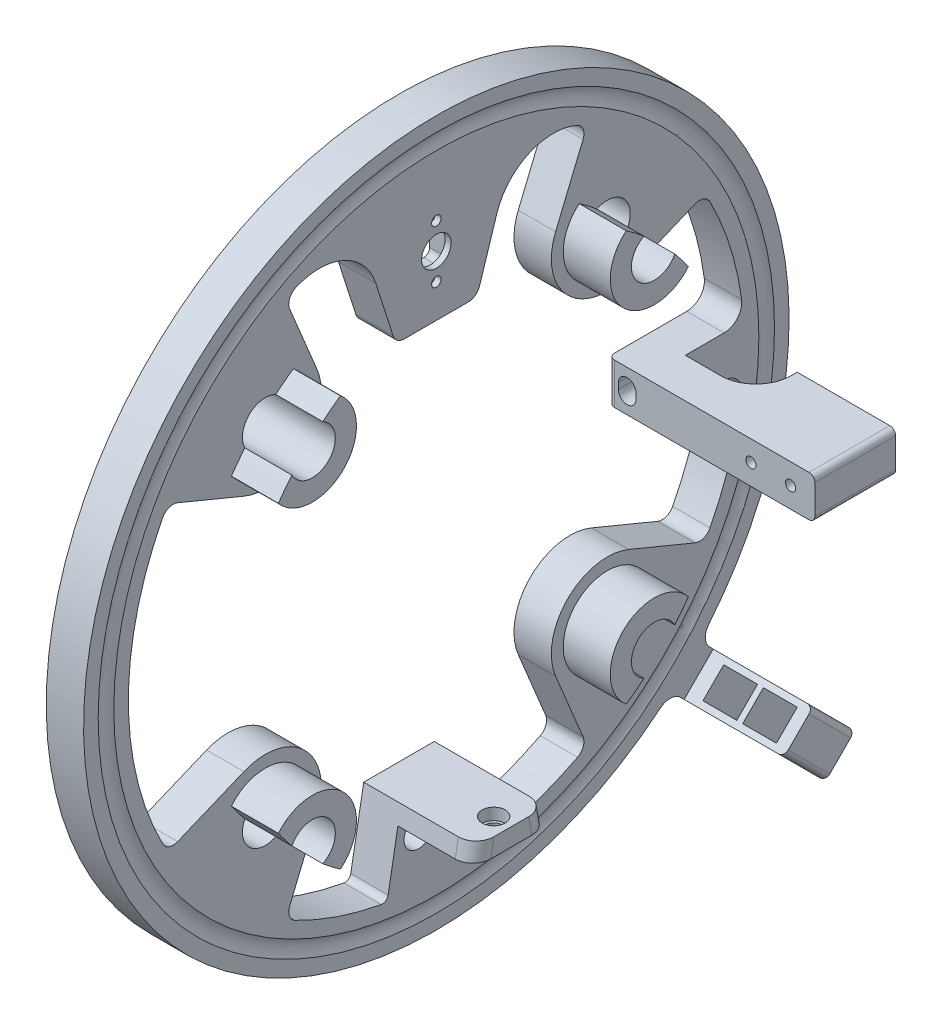
SolidWorks part; units mm, degrees
ref_plane "Front Plane" through (0, 0, 0) normal (0, 0, 1) x (1, 0, 0)
ref_plane "Top Plane" through (0, 0, 0) normal (0, 1, 0) x (1, 0, 0)
ref_plane "Right Plane" through (0, 0, 0) normal (1, 0, 0) x (0, 0, -1)
sketch "Sketch8" plane through (0, 0, 0) normal (1, 0, 0) x (0, 0, -1)
  line L1 (60, 60) -> (-60, 60) construction
  line L2 (60, 60) -> (60, -60) construction
  line L3 (60, -60) -> (-60, -60) construction
  line L4 (-60, 60) -> (-60, -60) construction
  line L5 (60, 60) -> (-60, -60) construction
  line L6 (60, -60) -> (-60, 60) construction
  point P0 (0, 0)
  dimension "D1" = 120
sketch "Sketch1" plane through (0, 0, 0) normal (1, 0, 0) x (0, 0, -1)
  line L0 (-60, 0) -> (-56.19, 0) construction
  line L1 (-56.19, 0) -> (-52.38, 0) construction
  circle A0 centre (0, 0) radius 56.19 construction
  circle A1 centre (0, 0) radius 60
  circle A2 centre (0, 0) radius 52.38
  dimension "D1" = 112.38
  dimension "D2" = 120
extrude "Boss-Extrude1" add sketch "Sketch1" along normal blind 6.35
sketch "Sketch2" plane through (0, 0, 0) normal (-1, 0, 0) x (0, 0, 1)
  line L0 (-20.2833, 32.7284) -> (-28.5792, 52.7563)
  line L1 (-60, -60) -> (60, -60) construction
  line L2 (-60, -60) -> (-60, 60) construction
  line L3 (-60, 60) -> (60, 60) construction
  line L4 (60, -60) -> (60, 60) construction
  line L5 (-60, -60) -> (60, 60) construction
  line L6 (-60, 60) -> (60, -60) construction
  line L7 (-28.5792, 52.7563) -> (-52.7563, 28.5792)
  line L8 (-52.7563, 28.5792) -> (-32.7284, 20.2833)
  circle A0 centre (0, 0) radius 52.38 construction
  arc A1 (-32.7284, 20.2833) -> (-20.2833, 32.7284) centre (-29.0833, 29.0833) ccw
  circle A3 centre (0, 0) radius 60 construction
  circle A5 centre (-29.0833, 29.0833) radius 11.25 construction
  circle A6 centre (0, 0) radius 52.78 construction
  point P0 (0, 0)
  point P10 (-40.6678, 40.6678)
  dimension "D2" = 19.05
  dimension "D3" = 45
  dimension "D5" = 105.56
  dimension "D4" = 22.5
  dimension "D1" = 120
extrude "Boss-Extrude2" add sketch "Sketch2" against normal up to surface (6.35 mm away) up to face at (6.35, 0, -60)
sketch "Sketch3" plane through (6.35, 0, 0) normal (1, 0, 0) x (0, 0, -1)
  circle A0 centre (29.0833, 29.0833) radius 7.5
  arc A2 (20.2833, 32.7284) -> (32.7284, 20.2833) centre (29.0833, 29.0833) ccw construction
  dimension "D1" = 15
extrude "Boss-Extrude3" add sketch "Sketch3" along normal blind 8
sketch "Sketch4" plane through (14.35, 0, 0) normal (1, 0, 0) x (0, 0, -1)
  circle A0 centre (29.0833, 29.0833) radius 3.9
  circle A1 centre (29.0833, 29.0833) radius 7.5 construction
  dimension "D1" = 7.8
extrude "Cut-Extrude2" cut sketch "Sketch4" against normal through all contours A0
fillet "Fillet5" radius 2 2 edges at (3.175, 45.6727, -25.6451) (3.175, 25.6451, -45.6727)
ref_axis "Axis1" through (6.35, 0, 0) along (-1, 0, 0)
pattern_circular "CirPattern1" count 4 every 90 about axis through (6.35, 0, 0) along (-1, 0, 0) of "Boss-Extrude3", "Boss-Extrude2", "Cut-Extrude2", "Fillet5"
sketch "Sketch5" plane through (0, 0, 0) normal (-1, 0, 0) x (0, 0, 1)
  line L0 (5.6388, 40) -> (-10.2587, 40) construction
  line L1 (0, 0) -> (0, 60) construction
  line L2 (15.871, 57.8629) -> (-15.871, 57.8629)
  line L3 (15.871, 57.8629) -> (6.9028, 29.8063)
  line L4 (6.9028, 29.8063) -> (-6.9028, 29.8063)
  line L5 (-15.871, 57.8629) -> (-6.9028, 29.8063)
  circle A0 centre (0, 40) radius 2.5
  circle A1 centre (0, 35.5) radius 0.8
  circle A2 centre (0, 44.5) radius 0.8
  circle A3 centre (0, 0) radius 60 construction
  dimension "D2" = 9
  dimension "D3" = 5
  dimension "D4" = 1.6
  dimension "D1" = 40
extrude "Boss-Extrude5" add sketch "Sketch5" against normal up to surface (6.35 mm away) up to face at (6.35, 36.5833, 29.0833)
sketch "Sketch6" plane through (0, 0, 0) normal (-1, 0, 0) x (0, 0, 1)
  line L1 (5.2, 33.8) -> (-5.2, 33.8)
  line L2 (5.2, 33.8) -> (5.2, 46.2)
  line L3 (5.2, 46.2) -> (-5.2, 46.2)
  line L4 (-5.2, 33.8) -> (-5.2, 46.2)
  line L5 (5.2, 33.8) -> (-5.2, 46.2) construction
  line L6 (5.2, 46.2) -> (-5.2, 33.8) construction
  point P0 (0, 40)
  dimension "D1" = 12.4
  dimension "D2" = 10.4
extrude "Cut-Extrude1" cut sketch "Sketch6" against normal offset from surface (5.35 mm away) 1 up to face at (6.35, 5.5549, 0)
fillet "Fillet1" radius 1 4 edges at (2.675, 33.8, 5.2) (2.675, 46.2, -5.2) (2.675, 46.2, 5.2) (2.675, 33.8, -5.2)
fillet "Fillet2" radius 10.08 2 edges at (3.175, 50.5974, -13.5486) (3.175, 50.5974, 13.5486)
fillet "Fillet3" radius 2 2 edges at (3.175, 29.8063, -6.9028) (3.175, 29.8063, 6.9028)
sketch "Sketch14" plane through (0, 0, 0) normal (-1, 0, 0) x (0, 0, 1)
  line L0 (-59.8978, 0) -> (0, 0) construction
  line L1 (-35.63, 3.5) -> (-59.8978, 3.5)
  line L2 (-35.63, 3.5) -> (-35.63, -3.5)
  line L3 (-35.63, -3.5) -> (-59.8978, -3.5)
  line L4 (-59.8978, 3.5) -> (-59.8978, -3.5)
  line L5 (-35.63, 3.5) -> (-59.8978, -3.5) construction
  line L6 (-35.63, -3.5) -> (-59.8978, 3.5) construction
  circle A0 centre (0, 0) radius 60 construction
  arc A2 (-46.5462, 24.0232) -> (-46.5462, -24.0232) centre (0, 0) ccw construction
  point P0 (-47.7639, 0)
  point P7 (-52.38, 0)
  dimension "D2" = 16.75
  dimension "D1" = 7
extrude "Boss-Extrude8" add sketch "Sketch14" against normal up to surface (6.35 mm away) up to face at (6.35, 6.7511, 0)
fillet "Fillet7" radius 3 2 edges at (3.175, -3.5, -52.2629) (3.175, 3.5, -52.2629)
sketch "Sketch7" plane through (0, 0, 0) normal (0, 1, 0) x (1, 0, 0)
  line L0 (8.636, 56.19) -> (-2.286, 56.19) construction
  line L1 (3.175, 60) -> (3.175, -60) construction
  line L2 (6.35, 60) -> (0, 60) construction
  line L3 (0, -60) -> (6.35, -60) construction
  circle A0 centre (8.636, 56.19) radius 2.645
  circle A1 centre (-2.286, 56.19) radius 2.645
  dimension "D1" = 5.29
  dimension "D2" = 56.19
  dimension "D3" = 10.922
revolve "Cut-Revolve1" cut sketch "Sketch7" angle 360 about axis through (6.35, 0, 0) along (-1, 0, 0)
sketch "Sketch9" plane through (0, 0, 0) normal (-1, 0, 0) x (0, 0, 1)
  line L0 (-54.1628, -49.2131) -> (-49.2131, -54.1628)
  line L1 (-49.2131, -54.1628) -> (-39.8793, -44.829)
  line L2 (-39.8793, -44.829) -> (-44.829, -39.8793)
  line L3 (-44.829, -39.8793) -> (-54.1628, -49.2131)
  line L4 (-60, -60) -> (60, 60) construction
  circle A0 centre (0, 0) radius 60 construction
  point P8 (-51.688, -51.688)
  dimension "D1" = 13.2
  dimension "D2" = 7
extrude "Boss-Extrude6" add sketch "Sketch9" against normal up to surface (6.35 mm away) up to face at (6.35, 0, -60)
fillet "Fillet6" radius 2.54 2 edges at (3.175, -44.829, -39.8793) (3.175, -39.8793, -44.829)
sketch "Sketch10" plane through (6.35, 0, 0) normal (1, 0, 0) x (0, 0, -1)
  line L0 (49.2131, -54.1628) -> (54.1628, -49.2131)
  line L1 (49.2131, -54.1628) -> (42.142, -47.0918)
  line L2 (54.1628, -49.2131) -> (47.0918, -42.142)
  line L3 (42.142, -47.0918) -> (47.0918, -42.142)
  dimension "D1" = 10
extrude "Boss-Extrude7" add sketch "Sketch10" along normal blind 17
sketch "Sketch11" plane through (0, -44.6169, -44.6169) normal (0, 0.7071, 0.7071) x (1, 0, 0)
  line L0 (6.35, 3.5) -> (6.35, -3.5) construction
  line L1 (8.85, 2.5) -> (14.6, 2.5)
  line L2 (8.85, 2.5) -> (8.85, -2.5)
  line L3 (8.85, -2.5) -> (14.6, -2.5)
  line L4 (14.6, 2.5) -> (14.6, -2.5)
  line L5 (8.85, 2.5) -> (14.6, -2.5) construction
  line L6 (8.85, -2.5) -> (14.6, 2.5) construction
  line L7 (23.35, 0) -> (6.35, 0) construction
  line L8 (23.35, 3.5) -> (23.35, -3.5) construction
  line L10 (15.6, 2.5) -> (21.35, 2.5)
  line L11 (15.6, 2.5) -> (15.6, -2.5)
  line L12 (15.6, -2.5) -> (21.35, -2.5)
  line L13 (21.35, 2.5) -> (21.35, -2.5)
  line L14 (15.6, 2.5) -> (21.35, -2.5) construction
  line L15 (15.6, -2.5) -> (21.35, 2.5) construction
  point P0 (11.725, 0)
  point P11 (18.475, 0)
  dimension "D1" = 2.5
  dimension "D2" = 5.75
  dimension "D3" = 5
  dimension "D4" = 1
extrude "Cut-Extrude3" cut sketch "Sketch11" against normal offset from surface (8.5 mm away) 1.5 up to face at (11.675, -51.688, -51.688)
sketch "Sketch12" plane through (0, -50.6273, -50.6273) normal (0, 0.7071, 0.7071) x (1, 0, 0)
  line L0 (15.6, -2.5) -> (21.35, 2.5) construction
  line L1 (8.85, -2.5) -> (14.6, 2.5) construction
  circle A0 centre (11.725, 0) radius 0.875
  circle A1 centre (18.475, 0) radius 0.875
  dimension "D1" = 1.75
extrude "Cut-Extrude4" cut sketch "Sketch12" against normal through all
sketch "Sketch15" plane through (6.35, 0, 0) normal (1, 0, 0) x (0, 0, -1)
  line L0 (48.9503, -3.5) -> (35.63, -3.5) construction
  line L1 (35.63, 3.5) -> (49.38, 3.5)
  line L2 (35.63, 3.5) -> (35.63, -3.5)
  line L3 (35.63, -3.5) -> (49.38, -3.5)
  line L4 (49.38, 3.5) -> (49.38, -3.5)
  dimension "D1" = 13.75
extrude "Boss-Extrude9" add sketch "Sketch15" along normal blind 28.75
sketch "Sketch16" plane through (0, 0, -49.38) normal (0, 0, -1) x (-1, 0, 0)
  line L0 (-35.1, 0) -> (-10.5477, 0) construction
  line L1 (-28.1, -2.5) -> (-33.85, -2.5)
  line L2 (-28.1, -2.5) -> (-28.1, 2.5)
  line L3 (-28.1, 2.5) -> (-33.85, 2.5)
  line L4 (-33.85, -2.5) -> (-33.85, 2.5)
  line L5 (-28.1, -2.5) -> (-33.85, 2.5) construction
  line L6 (-28.1, 2.5) -> (-33.85, -2.5) construction
  line L7 (-21.35, -2.5) -> (-27.1, -2.5)
  line L8 (-21.35, -2.5) -> (-21.35, 2.5)
  line L9 (-21.35, 2.5) -> (-27.1, 2.5)
  line L10 (-27.1, -2.5) -> (-27.1, 2.5)
  line L11 (-21.35, -2.5) -> (-27.1, 2.5) construction
  line L12 (-21.35, 2.5) -> (-27.1, -2.5) construction
  line L13 (-35.1, 3.5) -> (-35.1, -3.5) construction
  line L14 (-6.35, 0) -> (0, 0) construction
  line L15 (-14.6, -42.8491) -> (-8.85, -42.8491) construction
  line L18 (-6.35, -3.5) -> (-6.35, 3.5) construction
  point P0 (-30.975, 0)
  point P5 (-24.225, 0)
  dimension "D1" = 5
  dimension "D3" = 1
  dimension "D4" = 15
extrude "Cut-Extrude5" cut sketch "Sketch16" against normal offset from surface (12.25 mm away) 1.5 up to face at (17.55, 0, -35.63)
sketch "Sketch17" plane through (0, 0, -37.13) normal (0, 0, -1) x (-1, 0, 0)
  line L0 (-28.1, -2.5) -> (-33.85, 2.5) construction
  line L1 (-27.1, 2.5) -> (-21.35, -2.5) construction
  circle A0 centre (-30.975, 0) radius 0.875
  circle A1 centre (-24.225, 0) radius 0.875
  dimension "D1" = 1.75
extrude "Cut-Extrude6" cut sketch "Sketch17" against normal through all
fillet "Fillet8" radius 1 6 edges at (0, 0, -35.63) (0, -51.688, -51.688) (23.35, -45.6776, -50.6273) (23.35, -50.6273, -45.6776) (35.1, 3.5, -42.505) (35.1, -3.5, -42.505)
sketch "Sketch18" plane through (0, 0, 0) normal (0, 0, 1) x (1, 0, 0)
  line L1 (3.175, -0.5) -> (3.175, 0.5) construction
  line L3 (1.675, -0.5) -> (1.675, 0.5)
  line L4 (4.675, -0.5) -> (4.675, 0.5)
  line L5 (0, 0) -> (6.35, 0) construction
  line L6 (0, 60) -> (0, -60) construction
  line L7 (6.35, -60) -> (6.35, 60) construction
  arc A0 (1.675, -0.5) -> (4.675, -0.5) centre (3.175, -0.5) ccw
  arc A1 (4.675, 0.5) -> (1.675, 0.5) centre (3.175, 0.5) ccw
  point P2 (3.175, 0)
  dimension "D1" = 1.5
  dimension "D2" = 1
extrude "Cut-Extrude7" cut sketch "Sketch18" against normal through all
sketch "Sketch19" plane through (0, 0, 0) normal (-1, 0, 0) x (0, 0, 1)
  line L0 (0, -60) -> (0, -32.7201) construction
  line L1 (6, -38.38) -> (-6, -38.38)
  line L2 (6, -38.38) -> (8.5, -52.38)
  line L3 (8.5, -52.38) -> (-8.5, -52.38)
  line L4 (-6, -38.38) -> (-8.5, -52.38)
  line L5 (-60, -60) -> (60, -60) construction
  arc A0 (-24.0232, -46.5462) -> (24.0232, -46.5462) centre (0, 0) ccw construction
  circle A1 centre (3, -44) radius 2.5
  circle A2 centre (-3, -44) radius 2.5
  dimension "D1" = 5
  dimension "D2" = 16
  dimension "D5" = 6
  dimension "D3" = 12
  dimension "D4" = 17
  dimension "D6" = 5.62
extrude "Boss-Extrude10" add sketch "Sketch19" against normal up to surface (6.35 mm away) up to face at (6.35, 29.0833, -36.5833)
fillet "Fillet9" radius 1 2 edges at (3.175, -51.7054, -8.3795) (3.175, -51.7054, 8.3795)
sketch "Sketch20" plane through (14.35, 0, 0) normal (1, 0, 0) x (0, 0, -1)
  circle A0 centre (0, 0) radius 42.5
  circle A1 centre (0, 0) radius 60
  arc A2 (46.3255, -38.1306) -> (38.1306, -46.3255) centre (0, 0) ccw construction
  dimension "D1" = 85
extrude "Cut-Extrude8" cut sketch "Sketch20" against normal up to surface (8 mm away) and the other way blind 4 up to face at (6.35, -1.7736, -7.0879)
fillet "Fillet10" radius 6 1 edges at (18.35, 0, -42.5)
sketch "Sketch23" plane through (6.35, 0, 0) normal (1, 0, 0) x (0, 0, -1)
  line L0 (6, -38.38) -> (-6, -38.38)
  line L1 (-6, -38.38) -> (-6.5357, -41.38)
  line L2 (-8.2049, -50.7274) -> (-6, -38.38) construction
  line L3 (-6.5357, -41.38) -> (6.5357, -41.38)
  line L4 (6, -38.38) -> (8.2049, -50.7274) construction
  line L5 (6.5357, -41.38) -> (6, -38.38)
  dimension "D1" = 3
extrude "Boss-Extrude11" add sketch "Sketch23" along normal blind 12.75
fillet "Fillet11" radius 3 2 edges at (19.1, -39.88, -6.2679) (19.1, -39.88, 6.2679)
sketch "Sketch24" plane through (0, -38.38, 0) normal (0, 1, 0) x (1, 0, 0)
  line L0 (16.1, 0) -> (0, 0) construction
  line L1 (0, -6) -> (0, 6) construction
  circle A0 centre (16.1, 0) radius 1.95
  dimension "D1" = 3.9
  dimension "D2" = 9.75
extrude "Cut-Extrude9" cut sketch "Sketch24" against normal offset from surface (2 mm away) 1 up to face at (14.0571, -41.38, 0)
sketch "Sketch25" plane through (0, -40.38, 0) normal (0, 1, 0) x (1, 0, 0)
  circle A0 centre (16.1, 0) radius 1.5
  dimension "D1" = 3
extrude "Cut-Extrude10" cut sketch "Sketch25" against normal up to surface (1 mm away) up to face at (14.0571, -41.38, 0)
